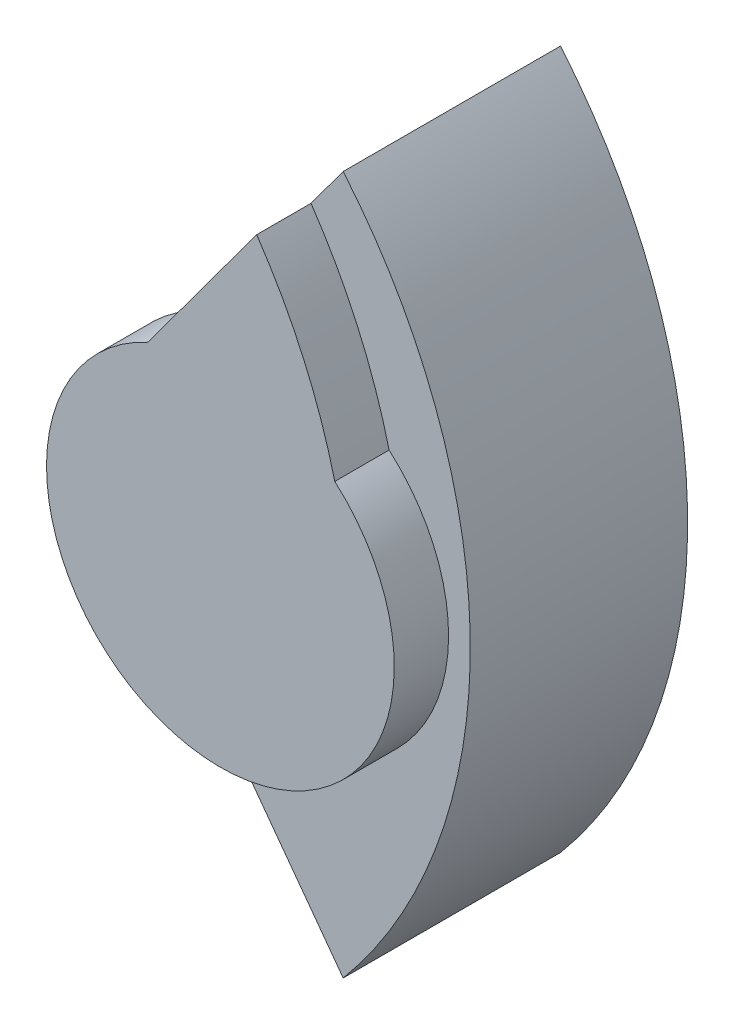
SolidWorks part; units mm, degrees
ref_plane "Front Plane" through (0, 0, 0) normal (0, 0, 1) x (1, 0, 0)
ref_plane "Top Plane" through (0, 0, 0) normal (0, 1, 0) x (1, 0, 0)
ref_plane "Right Plane" through (0, 0, 0) normal (1, 0, 0) x (0, 0, -1)
sketch "REF" plane through (0, 0, 0) normal (0, 0, 1) x (1, 0, 0)
  circle A0 centre (0, 0) radius 57.5 construction
  circle A1 centre (0, 0) radius 40 construction
  circle A2 centre (0, 0) radius 9 construction
  circle A3 centre (0, 0) radius 12 construction
  circle A4 centre (0, 0) radius 27.5 construction
  dimension "D1" = 115
  dimension "D2" = 80
  dimension "D3" = 24
  dimension "D4" = 18
  dimension "D5" = 55
sketch "Sketch3" plane through (0, 0, 0) normal (0, 0, 1) x (1, 0, 0)
  line L0 (0, 0) -> (32, 0) construction
  line L1 (0, 0) -> (38.3022, 32.1394) construction
  line L2 (38.3022, 32.1394) -> (20.7316, 8.3081)
  line L3 (38.3022, -32.1394) -> (20.7316, -8.3081)
  circle A0 centre (32, 0) radius 12 construction
  arc A1 (38.3022, 32.1394) -> (38.3022, -32.1394) centre (0, 0) cw
  circle A2 centre (32, 0) radius 14
  arc A3 (37.3499, 30.8478) -> (37.3499, -30.8478) centre (-2, 0) cw
  dimension "D2" = 24
  dimension "D3" = 50
  dimension "D4" = 28
  dimension "D6" = 2
  dimension "D1" = 32
  dimension "D5" = 40
extrude "Boss-Extrude1" add sketch "Sketch3" along normal blind 5 contours A2
extrude "Boss-Extrude2" add sketch "Sketch3<3>" against normal blind 3 contours A3 L2 A2 L3 | A2 | L2 A3 L3 A1 region at (49.3449, 0, 0) region at (47.3255, 0, 0) region at (32, 0, 0)
sketch "Sketch3<3>" plane through (0, 0, 0) normal (0, 0, 1) x (1, 0, 0) same geometry as "Sketch3"
extrude "Boss-Extrude3" add sketch "Sketch3<4>" against normal blind 20 contours L2 A3 L3 A1 region at (49.3449, 0, 0)
sketch "Sketch3<4>" plane through (0, 0, 0) normal (0, 0, 1) x (1, 0, 0) same geometry as "Sketch3"
extrude "Boss-Extrude4" add sketch "Sketch3<5>" against normal blind 20 contours A2
sketch "Sketch3<5>" plane through (0, 0, 0) normal (0, 0, 1) x (1, 0, 0) same geometry as "Sketch3"
sketch "Sketch4" plane through (0, 0, 0) normal (0, 0, 1) x (1, 0, 0)
  line L0 (38.3022, 32.1394) -> (20.7316, 8.3081) construction
  line L1 (35.3411, 28.1232) -> (25.3283, 14.5427)
  circle A0 centre (32, 0) radius 16
  arc A1 (35.3411, 28.1232) -> (42.5263, 12.0498) centre (-6, 0) cw
  line M1 (38.3022, 32.1394) -> (20.7316, 8.3081)
  arc M2 (20.7316, 8.3081) -> (20.7316, -8.3081) centre (32, 0) cw
  line M3 (20.7316, -8.3081) -> (38.3022, -32.1394)
  dimension "D1" = 32
  dimension "D2" = 50
  dimension "D3" = 4
extrude "Boss-Extrude5" add sketch "Sketch4" along normal blind 5 contours A1 A0 M1 | A0 M3 M1 M2 | A0 M1 M3 M2 region at (34.8978, 19.501, 0) region at (30.8917, 0, 0) region at (34.235, 15.4184, 0)
equation "\"tyre_ID\"= 115mm"
equation "\"disc_OD\" = 80mm"
equation "\"discbell_OD\" = 55mm"
equation "\"hub_OD\" = 40"
equation "\"bearing_ID\" = 25mm"
equation "\"shaft_OD\"= 19mm"
equation "\"D1@REF\" = \"tyre_ID\""
equation "\"D2@REF\" = \"disc_OD\""
equation "\"D5@REF\"=\"discbell_OD\""
